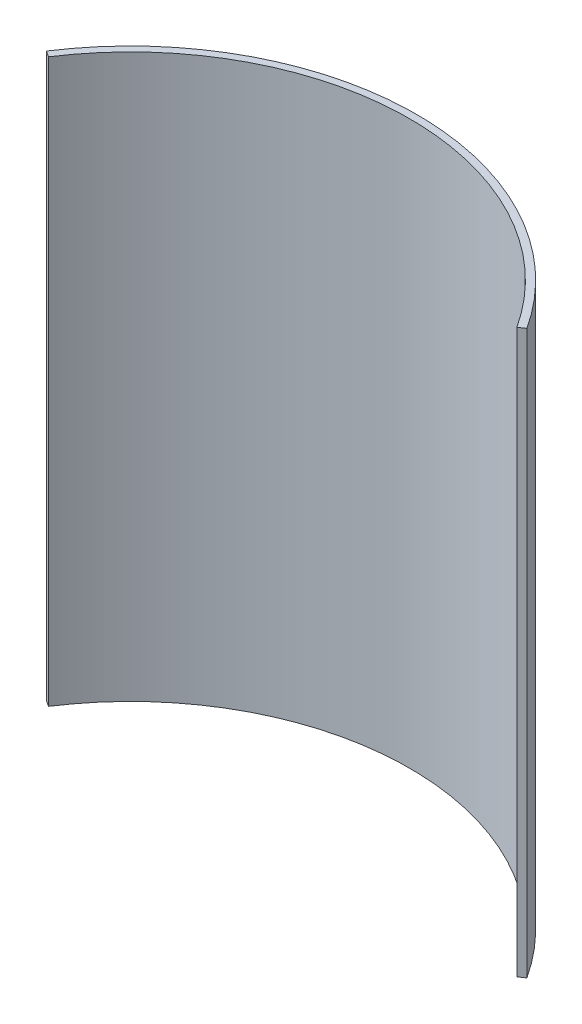
SolidWorks part; units mm, degrees
ref_plane "Front Plane" through (0, 0, 0) normal (0, 0, 1) x (1, 0, 0)
ref_plane "Top Plane" through (0, 0, 0) normal (0, 1, 0) x (1, 0, 0)
ref_plane "Right Plane" through (0, 0, 0) normal (1, 0, 0) x (0, 0, -1)
sketch "Sketch1" plane through (0, 0, 0) normal (0, 1, 0) x (1, 0, 0)
  line L0 (0, 45.7344) -> (0, 0) construction
  line L1 (32.1018, 19.4227) -> (31.43, 20.4549) construction
  line L3 (-31.43, 20.4549) -> (-32.2437, 20.9844)
  line L4 (39.6072, -22.8672) -> (0, 0) construction
  line L7 (-39.6072, -22.8672) -> (0, 0) construction
  line L8 (31.43, 20.4549) -> (32.2437, 20.9844)
  arc A2 (32.2437, 20.9844) -> (-32.2437, 20.9844) centre (0, 0) ccw
  arc A3 (31.43, 20.4549) -> (-31.43, 20.4549) centre (0, 0) ccw
  arc A4 (31.4297, 19.878) -> (-31.4297, 19.878) centre (0, -0.5774) ccw construction
  point P6 (0, 0)
  dimension "D1" = 74.539
  dimension "D4" = 3
extrude "Boss-Extrude1" add sketch "Sketch1" against normal blind 75.5
